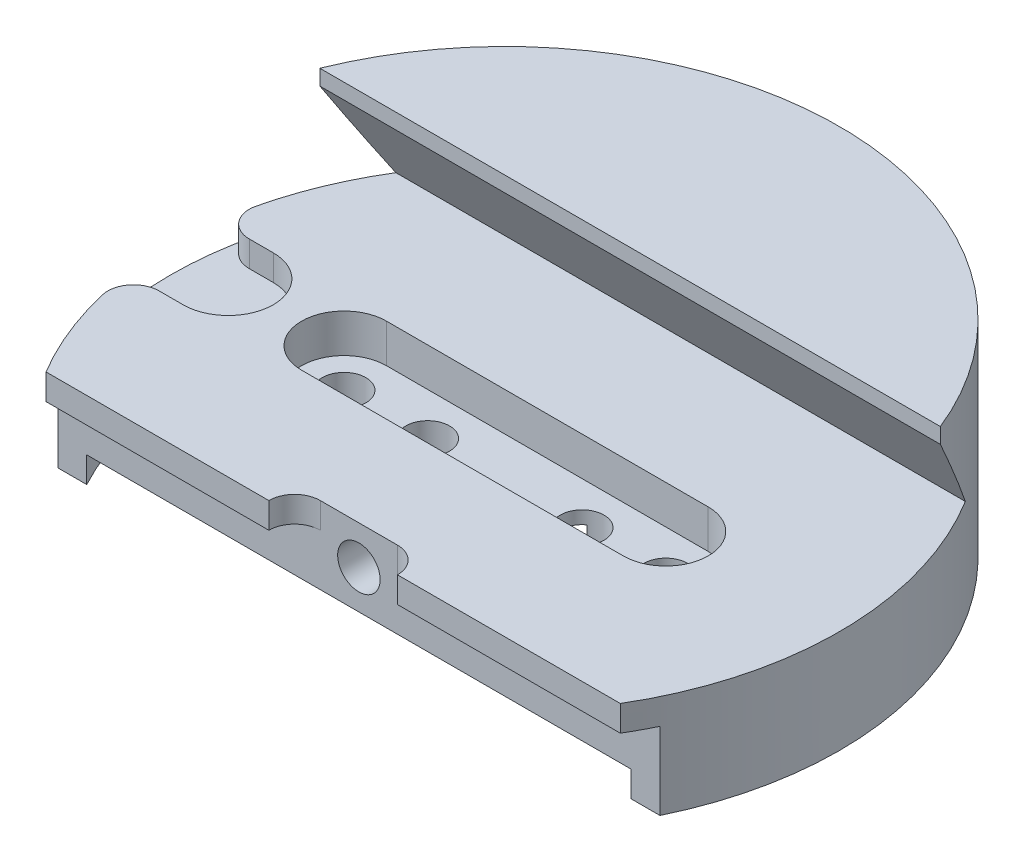
SolidWorks part; units mm, degrees
material "3.1355 (EN-AW 2024)"
ref_plane "Спереди" through (0, 0, 0) normal (0, 0, 1) x (1, 0, 0)
ref_plane "Сверху" through (0, 0, 0) normal (0, 1, 0) x (1, 0, 0)
ref_plane "Справа" through (0, 0, 0) normal (1, 0, 0) x (0, 0, -1)
sketch "Эскиз1" plane through (0, 0, 0) normal (0, 1, 0) x (1, 0, 0)
  circle A0 centre (0, 0) radius 26
  dimension "D1" = 52
extrude "Бобышка-Вытянуть1" add sketch "Эскиз1" along normal blind 14
sketch "Эскиз2" plane through (0, 0, 0) normal (1, 0, 0) x (0, 0, -1)
  line L0 (0, 14) -> (0, 0) construction
  line L1 (26, 14) -> (-26, 14) construction
  line L2 (13.6547, 6) -> (-13.6547, 6)
  line L3 (-13.6547, 6) -> (-9.7287, 12.8)
  line L4 (-9.7287, 12.8) -> (-9.7287, 14)
  line L5 (-9.7287, 14) -> (9.7287, 14)
  line L6 (0, 14) -> (0, 6) construction
  line L7 (13.6547, 6) -> (9.7287, 12.8)
  line L8 (9.7287, 12.8) -> (9.7287, 14)
  line L9 (-12.5, 8) -> (-12.5, 6) construction
  dimension "D1" = 8
  dimension "D2" = 1.2
  dimension "D3" = 60
  dimension "D4" = 13.6547
  dimension "D5" = 9.7287
  dimension "D6" = 2
  dimension "D7" = 12.5
extrude "Вырез-Вытянуть1" cut sketch "Эскиз2" against normal mid plane 60
sketch "Эскиз6" plane through (0, 6, 0) normal (0, 1, 0) x (1, 0, 0)
  line L1 (18.4208, 0) -> (-15.4735, 0) construction
  circle A0 centre (0, 0) radius 6 construction
  circle A1 centre (0, 0) radius 12.5 construction
  dimension "D1" = 12
  dimension "D2" = 25
hole_wizard "Цековка для винта с внутренним шестигранником M32" positions "Эскиз14" profile "Эскиз13" counterbore size "M3" standard "Ansi Metric" end condition up to next
sketch "Эскиз14" plane through (0, 6, 0) normal (0, 1, 0) x (1, 0, 0)
  line L0 (18.4208, 0) -> (-15.4735, 0) construction
  circle A0 centre (0, 0) radius 12.5 construction
  circle A1 centre (0, 0) radius 6 construction
  point P0 (-12.5, 0)
  point P6 (12.5, 0)
  point P20 (-6, 0)
  point P24 (6, 0)
sketch "Эскиз13" plane through (-12.5, 6, 0) normal (1, 0, 0) x (0, 0, 1)
  line L0 (0, 0) -> (0, 6)
  line L1 (0, 6) -> (1.7, 6)
  line L3 (1.7, 6) -> (1.7, 3)
  line L4 (1.7, 3) -> (3.3, 3)
  line L5 (3.3, 3) -> (3.3, 0)
  line L7 (3.3, 0) -> (0, 0)
  line L11 (0, -6.35) -> (0, 107.95) construction
  dimension "Диаметр сквозного отверстия" = 3.4
  dimension "Глубина сквозного отверстия" = 6
  dimension "Диаметр цековки" = 6.6
  dimension "Глубина цековки" = 3
sketch "Эскиз12" plane through (0, 0, 0) normal (0, -1, 0) x (1, 0, 0)
  circle A0 centre (0, 0) radius 26 construction
  circle A1 centre (0, 0) radius 26
  circle A3 centre (0, 0) radius 24
  dimension "D1" = 2
extrude "Бобышка-Вытянуть2" add sketch "Эскиз12" along normal blind 2
sketch "Эскиз17" plane through (0, 14, 0) normal (0, 1, 0) x (1, 0, 0)
  line L0 (-24.1112, -9.7287) -> (24.1112, -9.7287) construction
  line L1 (-24.1112, -9.7287) -> (24.1112, -9.7287)
  arc A0 (-24.1112, -9.7287) -> (24.1112, -9.7287) centre (0, 0) ccw construction
  arc A1 (-24.1112, -9.7287) -> (24.1112, -9.7287) centre (0, 0) ccw
extrude "Вырез-Вытянуть4" cut sketch "Эскиз17" against normal up to surface (8 mm away) up to face at (9.25, 6, 0)
sketch "Эскиз19" plane through (0, 6, 0) normal (0, 1, 0) x (1, 0, 0)
  line L0 (-22.3137, -13.3453) -> (22.3137, -13.3453)
  line L1 (-22.1258, 13.6547) -> (22.1258, 13.6547) construction
  arc A0 (-22.1258, 13.6547) -> (22.1258, 13.6547) centre (0, 0) ccw construction
  arc A1 (-22.3137, -13.3453) -> (22.3137, -13.3453) centre (0, 0) ccw
  dimension "D1" = 27
extrude "Вырез-Вытянуть6" cut sketch "Эскиз19" against normal blind 10
sketch "Эскиз21" plane through (0, 0, 13.3453) normal (0, 0, 1) x (1, 0, 0)
  line L0 (0, 0) -> (0, 6) construction
  line L1 (19.9475, 0) -> (-19.9475, 0) construction
  line L2 (22.3137, 6) -> (-22.3137, 6) construction
  point P6 (0, 3)
  dimension "D1" = 3
hole_wizard "Отверстие обработанное метчиком M4x0.71" positions "Эскиз23" profile "Эскиз22" tap size "M4x0.7" standard "Ansi Metric"
sketch "Эскиз23" plane through (0, 0, 13.3453) normal (0, 0, 1) x (1, 0, 0)
  point P4 (0, 3)
sketch "Эскиз22" plane through (0, 3, 13.3453) normal (1, 0, 0) x (0, -1, 0)
  line L0 (0, 0) -> (0, 12.4914)
  line L1 (0, 12.4914) -> (1.65, 11.5)
  line L2 (1.65, 11.5) -> (1.65, 0)
  line L5 (1.65, 0) -> (0, 0)
  line L10 (0, 12.4914) -> (-1.65, 11.5) construction
  line L11 (0, -6.35) -> (0, 107.95) construction
  dimension "Диаметр сверла" = 3.3
  dimension "Глубина сверла" = 11.5
  dimension "Угол заточки сверла" = 118
cosmetic thread "Отверстие резьбы1" parameters "D1"=8, "D2"=4
sketch "Эскиз20" plane through (0, 0, 13.3453) normal (0, 0, 1) x (1, 0, 0)
  line L0 (0, 3.1198) -> (0, -5.6063) construction
  line L1 (22.3137, 6) -> (-22.3137, 6) construction
  line L2 (-25.2656, 4) -> (-5, 4)
  line L3 (-25.2656, 4) -> (-25.2656, -2)
  line L4 (-25.2656, -2) -> (25.2656, -2)
  line L5 (25.2656, 4) -> (25.2656, -2)
  line L6 (-25.2656, 4) -> (25.2656, -2) construction
  line L7 (-25.2656, -2) -> (25.2656, 4) construction
  line L8 (-22.3137, -2) -> (-19.9475, -2) construction
  line L9 (-22.1258, 6) -> (22.1258, 6) construction
  line L11 (-5, 4) -> (-5, 6)
  line L12 (-5, 6) -> (5, 6)
  line L14 (-5, -4) -> (5, 6) construction
  line L15 (-5, 6) -> (5, -4) construction
  line L16 (5, 4) -> (25.2656, 4)
  line L17 (5, 4) -> (5, 6)
  point P3 (0, 1)
  point P12 (0, 1)
  dimension "D1" = 2
  dimension "D2" = 10
extrude "Вырез-Вытянуть7" cut sketch "Эскиз20" against normal blind 2
sketch "Эскиз24" plane through (0, 6, 0) normal (0, 1, 0) x (1, 0, 0)
  line L0 (-30.5, 0) -> (-21.5, 0) construction
  line L1 (-30.5, 3.5) -> (-21.5, 3.5)
  line L2 (-30.5, -3.5) -> (-21.5, -3.5)
  line L4 (0, 0) -> (-6.6582, 0) construction
  arc A0 (-22.1258, 13.6547) -> (-22.3137, -13.3453) centre (0, 0) ccw construction
  arc A1 (-30.5, 3.5) -> (-30.5, -3.5) centre (-30.5, 0) ccw
  arc A2 (-21.5, -3.5) -> (-21.5, 3.5) centre (-21.5, 0) ccw
  point P5 (-26, 0)
  dimension "D1" = 9
  dimension "D2" = 7
extrude "Вырез-Вытянуть8" cut sketch "Эскиз24" against normal blind 2
fillet "Скругление3" radius 2 2 edges at (-25.7633, 5, 3.5) (-25.7633, 5, -3.5)
sketch "Эскиз26" plane through (0, 6, 0) normal (0, 1, 0) x (1, 0, 0)
  line L0 (-12.5, 0) -> (12.5, 0) construction
  line L1 (-12.5, 3.3) -> (12.5, 3.3)
  line L2 (-12.5, -3.3) -> (12.5, -3.3)
  arc A0 (-12.5, 3.3) -> (-12.5, -3.3) centre (-12.5, 0) ccw
  arc A1 (12.5, -3.3) -> (12.5, 3.3) centre (12.5, 0) ccw
  arc A2 (9.25, -0.5723) -> (9.25, 0.5723) centre (12.5, 0) ccw construction
  point P2 (0, 0)
extrude "Вырез-Вытянуть9" cut sketch "Эскиз26" against normal up to surface (3 mm away)
sketch "Эскиз27" plane through (0, 0, 0) normal (0, -1, 0) x (1, 0, 0)
  line L0 (-23.1584, -6.3) -> (23.1584, -6.3)
  line L1 (12.5, -3.3) -> (-12.5, -3.3) construction
  arc A0 (-23.1584, -6.3) -> (23.1584, -6.3) centre (0, 0) ccw
  arc A1 (-21.1491, 11.3453) -> (21.1491, 11.3453) centre (0, 0) ccw construction
  dimension "D1" = 3
extrude "Вырез-Вытянуть10" cut sketch "Эскиз27" against normal offset from surface (4 mm away) 2 up to face at (-9.6316, 6, 3.4802)
sketch "Эскиз28" plane through (0, 0, 0) normal (0, -1, 0) x (1, 0, 0)
  line L0 (-5, 0) -> (-5, -6.3)
  line L1 (23.1584, -6.3) -> (-23.1584, -6.3) construction
  line L2 (-5, -6.3) -> (5, -6.3)
  line L3 (5, -6.3) -> (5, 0)
  arc A0 (5, 0) -> (-5, 0) centre (0, 0) ccw
  dimension "D1" = 10
extrude "Вырез-Вытянуть11" cut sketch "Эскиз28" against normal blind 2
fillet "Скругление4" radius 2 2 edges at (-5, 1, -6.3) (5, 1, -6.3)
sketch "Эскиз29" plane through (0, 4, 0) normal (0, -1, 0) x (1, 0, 0)
  line L0 (0, 0) -> (0, -18.738) construction
  line L1 (-9.5, -17) -> (9.5, -17) construction
  point P5 (0, -17)
  dimension "D1" = 19
  dimension "D2" = 17
hole_wizard "Отверстие обработанное метчиком M2.5x0.451" positions "Эскиз31" profile "Эскиз30" tap size "M2.5x0.45" standard "Ansi Metric"
sketch "Эскиз31" plane through (0, 4, 0) normal (0, -1, 0) x (-1, 0, 0)
  point P0 (9.5, 17)
  point P3 (-9.5, 17)
sketch "Эскиз30" plane through (-9.5, 4, -17) normal (1, 0, 0) x (0, 0, -1)
  line L0 (0, 0) -> (0, 3.6159)
  line L1 (0, 3.6159) -> (1.025, 3)
  line L2 (1.025, 3) -> (1.025, 0)
  line L5 (1.025, 0) -> (0, 0)
  line L10 (0, 3.6159) -> (-1.025, 3) construction
  line L11 (0, -6.35) -> (0, 107.95) construction
  dimension "Диаметр сверла" = 2.05
  dimension "Глубина сверла" = 3
  dimension "Угол заточки сверла" = 118
cosmetic thread "Отверстие резьбы2" parameters "D1"=3, "D2"=2.5
cosmetic thread "Отверстие резьбы3" parameters "D1"=3, "D2"=2.5
sketch "Эскиз32" plane through (0, 4, 0) normal (0, -1, 0) x (1, 0, 0)
  line L0 (-7.8712, -22.5667) -> (-4.5, -15.6547)
  line L1 (-4.5, -15.6547) -> (4.5, -15.6547)
  line L2 (4.5, -15.6547) -> (7.8712, -22.5667)
  line L3 (-22.1258, -13.6547) -> (22.1258, -13.6547) construction
  arc A0 (-7.8712, -22.5667) -> (7.8712, -22.5667) centre (0, 0) ccw
  point P4 (0, -15.6547)
  point P7 (0, -23.9)
  dimension "D1" = 23.9
  dimension "D2" = 9
  dimension "D3" = 2
  dimension "D4" = 116
extrude "Вырез-Вытянуть12" cut sketch "Эскиз32" against normal offset from surface (8 mm away) 2 up to face at (0, 14, -17.8644)
fillet "Скругление5" radius 2 4 edges at (-4.5, 8, -15.6547) (4.5, 8, -15.6547) (7.8712, 8, -22.5667) (-7.8712, 8, -22.5667)
fillet "Скругление6" radius 2 4 edges at (-5, 5, 11.3453) (5, 5, 11.3453) (-23.1584, 2, -6.3) (23.1584, 2, -6.3)
